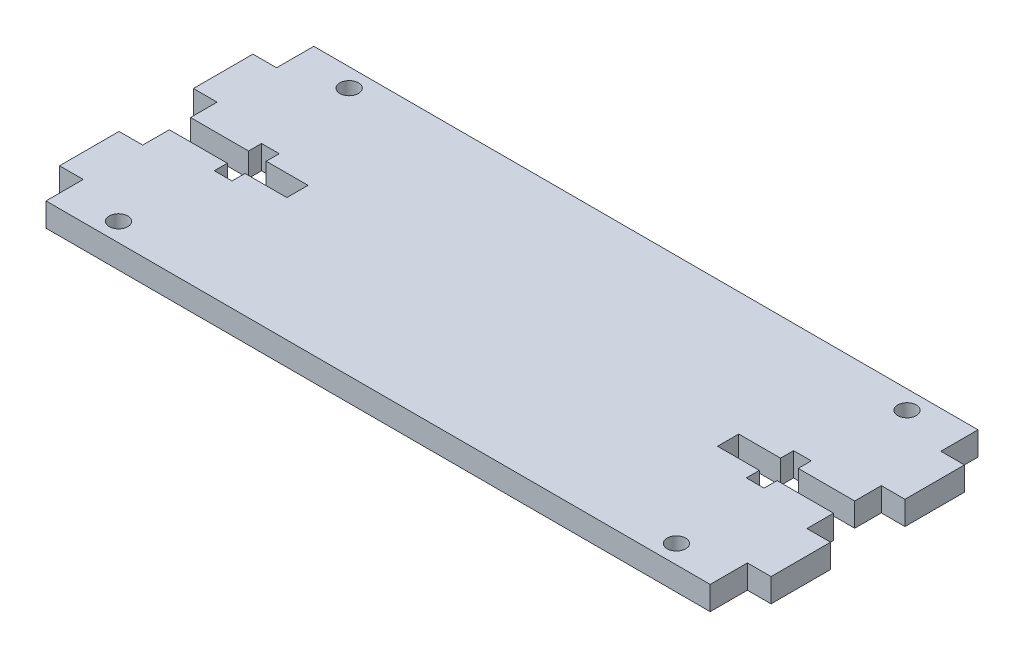
SolidWorks part; units mm, degrees
ref_plane "Front Plane" through (0, 0, 0) normal (0, 0, 1) x (1, 0, 0)
ref_plane "Top Plane" through (0, 0, 0) normal (0, 1, 0) x (1, 0, 0)
ref_plane "Right Plane" through (0, 0, 0) normal (1, 0, 0) x (0, 0, -1)
sketch "Sketch1" plane through (0, 0, 0) normal (0, 1, 0) x (1, 0, 0)
  line L0 (40, -15.5) -> (40, 15.5) construction
  line L1 (37.5, 18) -> (-37.5, 18)
  line L2 (-40, 15.5) -> (-40, -15.5) construction
  line L3 (-37.5, -18) -> (37.5, -18)
  line L4 (34.35, -2.25) -> (34.35, 17.05) construction
  line L5 (34.35, 17.05) -> (-7.65, 17.05) construction
  line L6 (-7.65, 17.05) -> (-7.65, -2.25) construction
  line L7 (-7.65, -2.25) -> (34.35, -2.25) construction
  line L8 (40, 18) -> (40, 15.5) construction
  line L9 (37.5, 18) -> (40, 18)
  line L10 (-40, 15.5) -> (-40, 18) construction
  line L11 (-40, 18) -> (-37.5, 18)
  line L12 (-40, -18) -> (-40, -15.5) construction
  line L13 (-37.5, -18) -> (-40, -18)
  line L14 (40, -18) -> (37.5, -18)
  line L15 (40, -15.5) -> (40, -18) construction
  line L16 (44.5392, 18) -> (44.5392, 13)
  line L17 (-44.7508, 18) -> (-44.7508, 13)
  line L18 (44.5392, 13) -> (47.7192, 13)
  line L19 (-44.7508, 13) -> (-47.9308, 13)
  line L20 (47.7192, 13) -> (47.7192, 5)
  line L21 (47.7192, 5) -> (44.5392, 5)
  line L22 (44.5392, 5) -> (44.5392, -5)
  line L23 (44.5392, -5) -> (47.7192, -5)
  line L24 (47.7192, -5) -> (47.7192, -13)
  line L25 (47.7192, -13) -> (44.5392, -13)
  line L26 (44.5392, -13) -> (44.5392, -18)
  line L27 (47.7192, 13) -> (47.7192, 5)
  line L28 (47.7192, -5) -> (47.7192, -13)
  line L30 (40, 18) -> (44.5392, 18)
  line L32 (44.5392, -18) -> (40, -18)
  line L33 (-40, 18) -> (-44.7508, 18)
  line L34 (-47.9308, 13) -> (-47.9308, 5)
  line L35 (-44.7508, -18) -> (-40, -18)
  line L36 (-47.9308, 5) -> (-44.7508, 5)
  line L37 (-44.7508, 5) -> (-44.7508, -5)
  line L38 (-44.7508, -5) -> (-47.9308, -5)
  line L39 (-47.9308, -5) -> (-47.9308, -13)
  line L40 (-47.9308, -13) -> (-44.7508, -13)
  line L41 (-44.7508, -13) -> (-44.7508, -18)
  line L47 (-40, 18) -> (40, -18) construction
  line L48 (40, 18) -> (-40, -18) construction
  arc A0 (37.5, 18) -> (40, 15.5) centre (37.5, 15.5) ccw construction
  arc A1 (-40, 15.5) -> (-37.5, 18) centre (-37.5, 15.5) ccw construction
  arc A2 (-37.5, -18) -> (-40, -15.5) centre (-37.5, -15.5) ccw construction
  arc A3 (40, -15.5) -> (37.5, -18) centre (37.5, -15.5) ccw construction
  circle A4 centre (-37.5, 15.5) radius 1.25
  circle A5 centre (-37.5, -15.5) radius 1.25
  circle A6 centre (37.5, -15.5) radius 1.25
  circle A7 centre (37.5, 15.5) radius 1.25
extrude "Boss-Extrude1" add sketch "Sketch1" along normal blind 3.18 contours L40 L41 L35 L13 L3 L14 L32 L26 L25 L24 L23 L22 L21 L20 L18 L16 L30 L9 L1 L11 L33 L17 L19 L34 L36 L37 L38 L39 A7 A6 A5 A4 region at (-0.1065, 0, 0)
sketch "Sketch2" plane through (0, 3.18, 0) normal (0, 1, 0) x (1, 0, 0)
  line L17 (-44.7508, 5) -> (-44.7508, -5) construction
  line L18 (-44.7508, 1.425) -> (-36.9508, 1.425)
  line L19 (-36.9508, 1.425) -> (-36.9508, 3.175)
  line L20 (-36.9508, 3.175) -> (-34.5708, 3.175)
  line L21 (-34.5708, 3.175) -> (-34.5708, 1.425)
  line L22 (-34.5708, 1.425) -> (-28.9508, 1.425)
  line L23 (-28.9508, 1.425) -> (-28.9508, -1.425)
  line L24 (-28.9508, -1.425) -> (-34.5708, -1.425)
  line L25 (-34.5708, -1.425) -> (-34.5708, -3.175)
  line L26 (-34.5708, -3.175) -> (-36.9508, -3.175)
  line L27 (-36.9508, -3.175) -> (-36.9508, -1.425)
  line L28 (-36.9508, -1.425) -> (-44.7508, -1.425)
  line L29 (-44.7508, -1.425) -> (-44.7508, 1.425)
  line L30 (-44.7508, -5) -> (-47.9308, -5) construction
  dimension "D1" = 15.8
  dimension "D2" = 2.85
  dimension "D3" = 2.38
  dimension "D4" = 7.8
  dimension "D5" = 3.575
  dimension "D6" = 6.35
extrude "Cut-Extrude1" cut sketch "Sketch2" against normal through all
mirror "Mirror1" about plane through (0, 0, 0) normal (1, 0, 0) of "Cut-Extrude1"
